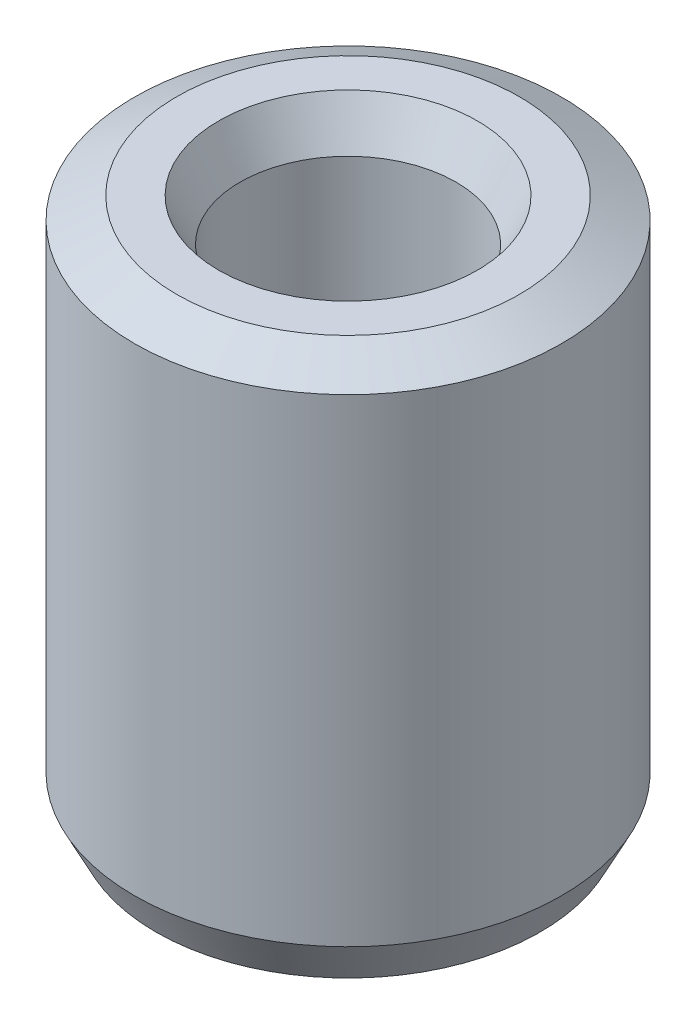
SolidWorks part; units mm, degrees
ref_plane "Front Plane" through (0, 0, 0) normal (0, 0, 1) x (1, 0, 0)
ref_plane "Top Plane" through (0, 0, 0) normal (0, 1, 0) x (1, 0, 0)
ref_plane "Right Plane" through (0, 0, 0) normal (1, 0, 0) x (0, 0, -1)
sketch "Sketch1" plane through (0, 0, 0) normal (0, 1, 0) x (1, 0, 0)
  circle A0 centre (0, 0) radius 15
  dimension "SLEEVE_OD" = 30
extrude "Boss-Extrude1" add sketch "Sketch1" along normal blind 38.0522
sketch "Sketch2" plane through (0, 0, 0) normal (0, 1, 0) x (1, 0, 0)
  circle A0 centre (0, 0) radius 7.5795
  dimension "BORE_D" = 15.1591
extrude "Cut-Extrude1" cut sketch "Sketch2" along normal through all
chamfer "Chamfer1" distance 1.5064 angle 63.09 4 edges at (0, 38.0522, 7.5795) (0, 0, 7.5795) (0, 0, 15) (0, 38.0522, 15) first distance on face at (0, 38.0522, 7.5795) first distance on face at (0, 0, 7.5795) first distance on face at (0, 38.0522, 15)
